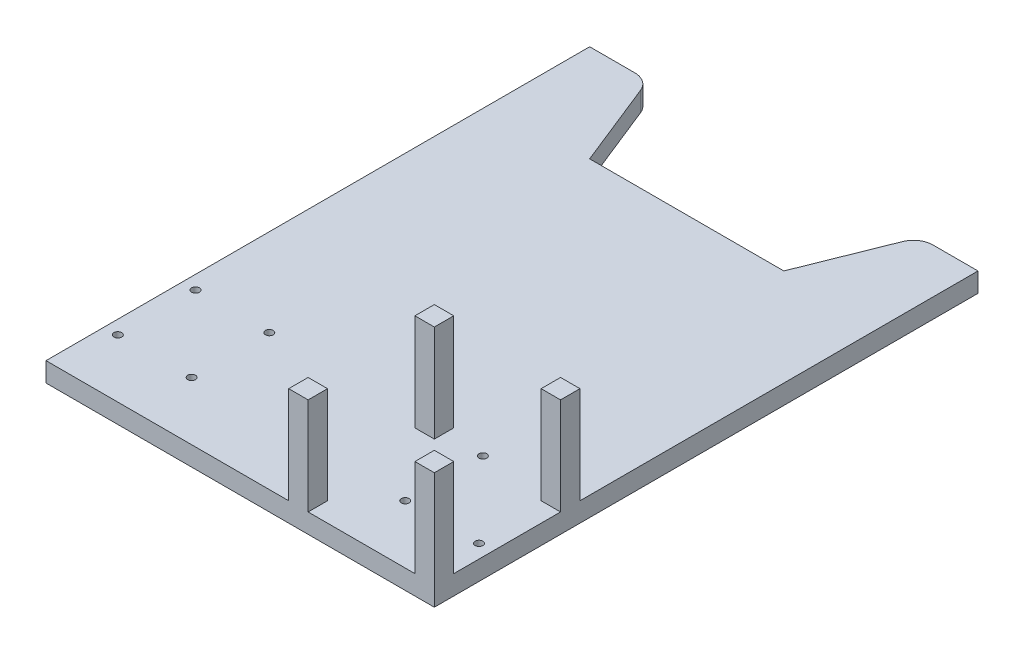
SolidWorks part; units mm, degrees
material "Pine"
ref_plane "Front Plane" through (0, 0, 0) normal (0, 0, 1) x (1, 0, 0)
ref_plane "Top Plane" through (0, 0, 0) normal (0, 1, 0) x (1, 0, 0)
ref_plane "Right Plane" through (0, 0, 0) normal (1, 0, 0) x (0, 0, -1)
sketch "Sketch3" plane through (0, 0, 0) normal (0, 1, 0) x (1, 0, 0)
  line L1 (-100, -140) -> (100, -140)
  line L2 (-100, -140) -> (-100, 140)
  line L3 (-100, 140) -> (100, 140)
  line L4 (100, -140) -> (100, 140)
  line L5 (-100, -140) -> (100, 140) construction
  line L6 (-100, 140) -> (100, -140) construction
  point P0 (0, 0)
  dimension "D1" = 200
  dimension "D2" = 280
extrude "Boss-Extrude1" add sketch "Sketch3" along normal blind 10
sketch "Sketch4" plane through (0, 10, 0) normal (0, 1, 0) x (1, 0, 0)
  line L0 (100, -140) -> (100, 140) construction
  line L1 (100, -140) -> (90, -140)
  line L2 (100, -140) -> (100, -130)
  line L3 (100, -65) -> (90, -65)
  line L4 (25, -140) -> (25, -130)
  line L5 (-100, -140) -> (100, -140) construction
  line L6 (35, -140) -> (35, -130)
  line L7 (90, -65) -> (90, -75)
  line L8 (35, -65) -> (25, -65)
  line L9 (35, -140) -> (25, -140)
  line L10 (25, -130) -> (35, -130)
  line L11 (25, -75) -> (35, -75)
  line L12 (90, -75) -> (100, -75)
  line L13 (90, -130) -> (100, -130)
  line L14 (25, -75) -> (25, -65)
  line L15 (35, -75) -> (35, -65)
  line L16 (90, -130) -> (90, -140)
  line L17 (100, -75) -> (100, -65)
  point P20 (95, -130)
  dimension "D1" = 0
  dimension "D2" = 0
  dimension "D3" = 75
  dimension "D4" = 75
  dimension "D5" = 10
  dimension "D6" = 10
  dimension "D7" = 10
  dimension "D8" = 10
  dimension "D9" = 10
extrude "Boss-Extrude2" add sketch "Sketch4" along normal blind 50
sketch "Sketch7" plane through (0, 0, 0) normal (0, -1, 0) x (1, 0, 0)
  line L0 (100, 140) -> (100, -140) construction
  line L1 (-100, 140) -> (100, 140) construction
  line L4 (-93, 70) -> (93, 70) construction
  line L5 (-93, 110) -> (93, 110) construction
  line L6 (-100, -140) -> (-100, 140) construction
  circle A8 centre (-93, 70) radius 2
  circle A9 centre (-93, 110) radius 2
  circle A10 centre (-55, 110) radius 2
  circle A11 centre (-55, 70) radius 2
  circle A12 centre (55, 110) radius 2
  circle A13 centre (93, 110) radius 2
  circle A14 centre (93, 70) radius 2
  circle A15 centre (55, 70) radius 2
  dimension "D17" = 40
  dimension "D4" = 7
  dimension "D1" = 38
  dimension "D2" = 40
  dimension "D3" = 38
  dimension "D5" = 38
  dimension "D6" = 40
  dimension "D7" = 38
  dimension "D16" = 7
  dimension "D18" = 55.1725
  dimension "D19" = 40
  dimension "D20" = 55.1725
  dimension "D27" = 30
extrude "Cut-Extrude2" cut sketch "Sketch7" against normal blind 10
sketch "Sketch8" plane through (0, 10, 0) normal (0, 1, 0) x (1, 0, 0)
  line L0 (-100, -140) -> (25, -140) construction
  line L1 (-100, 140) -> (-100, -140) construction
  line L2 (100, -65) -> (100, 140) construction
  circle A0 centre (-35, -35) radius 4
  circle A1 centre (-15, -35) radius 4
  circle A5 centre (-35, 40) radius 4
  circle A6 centre (-15, 40) radius 4
  circle A7 centre (45, 2.5) radius 4
  circle A8 centre (65, 2.5) radius 4
  dimension "D1" = 8
  dimension "D2" = 8
  dimension "D4" = 8
  dimension "D5" = 8
  dimension "D7" = 8
  dimension "D8" = 8
  dimension "D3" = 20
  dimension "D6" = 20
  dimension "D9" = 20
  dimension "D10" = 105
  dimension "D11" = 65
  dimension "D12" = 65
  dimension "D13" = 75
  dimension "D14" = 37.5
  dimension "D15" = 35
extrude "Cut-Extrude3" [suppressed] cut sketch "Sketch8" against normal blind 10
sketch "Sketch9" plane through (0, 10, 0) normal (0, 1, 0) x (1, 0, 0)
  line L0 (100, 140) -> (-100, 140) construction
  line L1 (50, 140) -> (-50, 140)
  line L3 (50, 90) -> (-50, 90)
  line L5 (50, 98.4245) -> (100, 98.4245) construction
  line L6 (100, -65) -> (100, 140) construction
  line L7 (-50, 98.4245) -> (-100, 98.4245) construction
  line L8 (-100, 140) -> (-100, -140) construction
  line L9 (50, 140) -> (70, 140)
  line L10 (70, 140) -> (50, 90)
  line L11 (-50, 140) -> (-70, 140)
  line L12 (-70, 140) -> (-50, 90)
  dimension "D1" = 100
  dimension "D2" = 50
  dimension "D3" = 20
  dimension "D4" = 20
extrude "Cut-Extrude4" cut sketch "Sketch9" against normal blind 10
fillet "Fillet1" radius 10 2 edges at (-70, 5, -140) (70, 5, -140)
